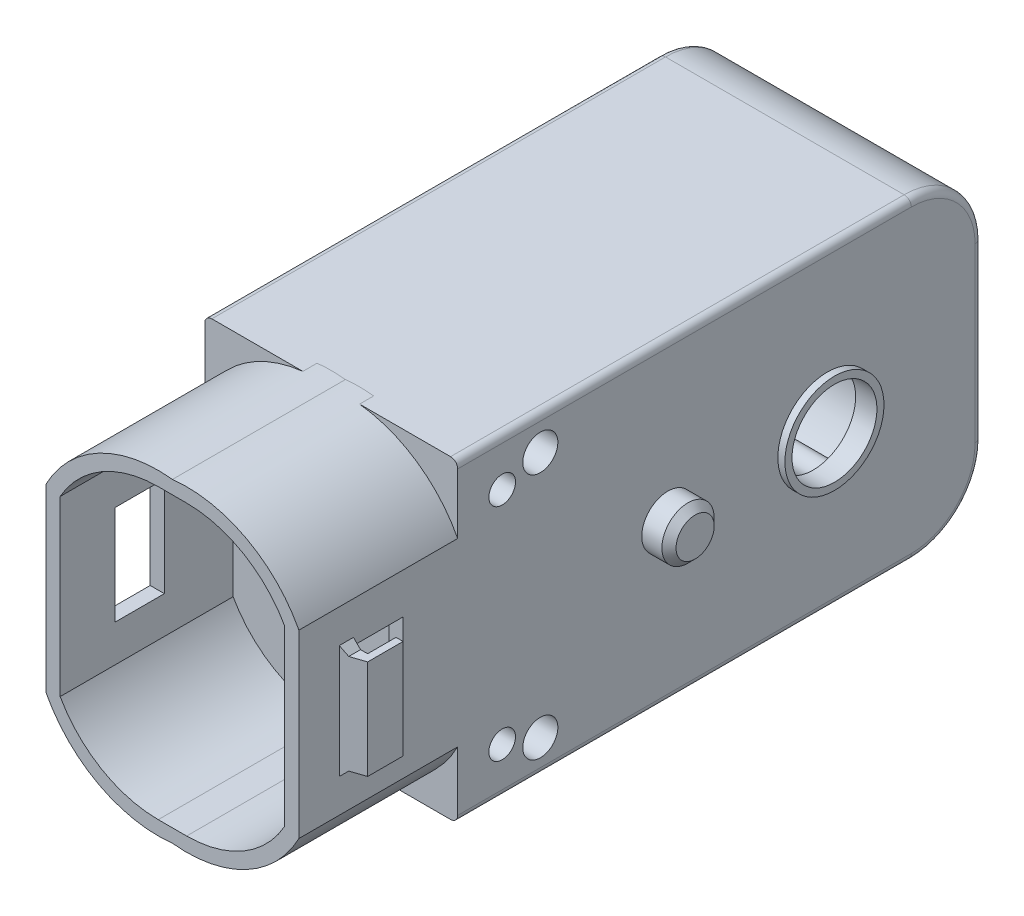
SolidWorks part; units mm, degrees
ref_plane "Front Plane" through (0, 0, 0) normal (0, 0, 1) x (1, 0, 0)
ref_plane "Top Plane" through (0, 0, 0) normal (0, 1, 0) x (1, 0, 0)
ref_plane "Right Plane" through (0, 0, 0) normal (1, 0, 0) x (0, 0, -1)
sketch "Sketch1" plane through (0, 0, 0) normal (0, 0, 1) x (1, 0, 0)
  line L0 (0, 11.115) -> (0, 10.1712)
  line L2 (-8.92, 6.365) -> (-8.92, -6.365)
  line L4 (-8.92, 6.365) -> (-8.92, -6.365) construction
  line L5 (55, 0) -> (-55, 0) construction
  line L7 (-7.92, 6.1126) -> (-7.92, -6.1126)
  line L8 (-1, 10.1712) -> (-1, -10.1712) construction
  line L9 (-1, 10.1712) -> (0, 10.1712)
  line L10 (-1, -10.1712) -> (0, -10.1712)
  line L11 (0, -10.1712) -> (0, -11.115)
  line L13 (0, 11.115) -> (0, -11.115) construction
  arc A0 (-8.92, 6.365) -> (0, 11.115) centre (-1, 2.2425) cw
  arc A1 (-8.92, -6.365) -> (0, -11.115) centre (-1, -2.2425) ccw
  arc A2 (-7.92, -6.1126) -> (-1, -10.1712) centre (-1, -2.2425) ccw
  arc A3 (-7.92, 6.1126) -> (-1, 10.1712) centre (-1, 2.2425) cw
  dimension "D1" = 22.23
  dimension "D2" = 12.73
  dimension "D3" = 1
extrude "Boss-Extrude1" add sketch "Sketch1" along normal blind 11.2
sketch "Sketch2" plane through (0, 0, 0) normal (0, 0, -1) x (-1, 0, 0)
  line L0 (0, -10.1712) -> (1, -10.1712) construction
  line L1 (2, 11.115) -> (8.92, 11.115)
  line L2 (0, 11.115) -> (0, 10.1712)
  line L3 (2.4484, -11.0529) -> (8.92, -11.0529)
  line L4 (8.92, 11.115) -> (8.92, -11.0529)
  line L5 (7.92, -6.1126) -> (7.92, 6.1126) construction
  line L6 (1, 10.1712) -> (0, 10.1712) construction
  line L7 (0, -10.1712) -> (1, -10.1712)
  line L8 (7.92, -6.1126) -> (7.92, 6.1126)
  line L9 (1, 10.1712) -> (0, 10.1712)
  line L10 (0, -10.1712) -> (0, -11.115)
  line L11 (8.92, 6.365) -> (8.92, -6.365) construction
  arc A0 (8.92, 6.365) -> (0, 11.115) centre (1, 2.2425) ccw construction
  arc A1 (2, 11.115) -> (0, 11.115) centre (1, 2.2425) ccw
  arc A2 (0, -11.115) -> (8.92, -6.365) centre (1, -2.2425) ccw construction
  arc A3 (0, -11.115) -> (2.4484, -11.0529) centre (1, -2.2425) ccw
  arc A4 (1, -10.1712) -> (7.92, -6.1126) centre (1, -2.2425) ccw construction
  arc A5 (7.92, 6.1126) -> (1, 10.1712) centre (1, 2.2425) ccw construction
  arc A6 (1, -10.1712) -> (7.92, -6.1126) centre (1, -2.2425) ccw
  arc A7 (7.92, 6.1126) -> (1, 10.1712) centre (1, 2.2425) ccw
extrude "Boss-Extrude2" add sketch "Sketch2" along normal blind 1
sketch "Sketch4" plane through (0, 0, -1) normal (0, 0, -1) x (-1, 0, 0)
  line L0 (0, -10.1712) -> (0, -11.115) construction
  line L1 (8.92, 11.115) -> (0, 11.115)
  line L2 (8.92, 11.115) -> (8.92, -11.0529)
  line L3 (8.92, -11.0529) -> (0, -11.0529)
  line L4 (0, 11.115) -> (0, 10.115)
  line L5 (2.4484, -11.0529) -> (8.92, -11.0529) construction
  line L6 (7.92, 10.115) -> (7.92, -10.0529)
  line L7 (7.92, -10.0529) -> (1, -10.0529)
  line L9 (7.92, 10.115) -> (1, 10.115)
  line L10 (1, 10.115) -> (0, 10.115)
  line L11 (1, -10.0529) -> (0, -10.0529)
  line L12 (0, -10.0529) -> (0, -11.0529)
  line L13 (1, 10.115) -> (1, -10.0529) construction
  line L15 (0, 11.115) -> (0, -11.0529) construction
  dimension "D1" = 1
extrude "Boss-Extrude4" add sketch "Sketch4" along normal blind 36
sketch "Sketch5" plane through (0, 0, -37) normal (0, 0, -1) x (-1, 0, 0)
  line L1 (0, 11.115) -> (8.92, 11.115)
  line L2 (0, 11.115) -> (0, -11.0529)
  line L3 (0, -11.0529) -> (8.92, -11.0529)
  line L4 (8.92, 11.115) -> (8.92, -11.0529)
extrude "Boss-Extrude6" add sketch "Sketch5" against normal blind 2
fillet "Fillet2" radius 5 4 edges at (-3.96, -10.0529, -35) (-3.96, 10.115, -35) (-4.46, -11.0529, -37) (-4.46, 11.115, -37)
sketch "Sketch6" plane through (0, 0, -37) normal (0, 0, -1) x (-1, 0, 0)
  line L0 (0, 0) -> (1.4, 0) construction
  line L1 (0, 6.115) -> (0, -6.0529) construction
  line L2 (1.4, -2.5) -> (0, -2.5)
  line L3 (1.4, -2.5) -> (1.4, 2.5)
  line L4 (1.4, 2.5) -> (0, 2.5)
  line L5 (0, -2.5) -> (0, 2.5)
  line L6 (1.4, -2.5) -> (0, 2.5) construction
  line L7 (1.4, 2.5) -> (0, -2.5) construction
  point P3 (0.7, 0)
  dimension "D1" = 1.4
  dimension "D2" = 5
extrude "Boss-Extrude7" add sketch "Sketch6" along normal blind 4.8
sketch "Sketch7" plane through (-1.4, 0, 0) normal (-1, 0, 0) x (0, 0, 1)
  line L0 (-39.4, 2.5) -> (-39.4, -2.5) construction
  line L1 (-41.8, 2.5) -> (-37, 2.5) construction
  line L2 (-41.8, -2.5) -> (-37, -2.5) construction
  line L3 (-37, -2.5) -> (-37, 2.5) construction
  circle A0 centre (-39.4, 0) radius 1.38
  dimension "D1" = 2.76
extrude "Cut-Extrude1" cut sketch "Sketch7" against normal blind 4.8
sketch "Sketch8" plane through (-8.92, 0, 0) normal (-1, 0, 0) x (0, 0, 1)
  line L0 (-37, 0) -> (-26.08, 0) construction
  line L1 (-37, -2.5) -> (-37, 2.5) construction
  circle A0 centre (-26.08, 0) radius 3.495
  circle A2 centre (-26.08, 0) radius 2.995
  dimension "D2" = 6.99
  dimension "D3" = 0.5
  dimension "D1" = 10.92
extrude "Boss-Extrude8" add sketch "Sketch8" along normal blind 0.5
sketch "Sketch9" plane through (-8.92, 0, 0) normal (-1, 0, 0) x (0, 0, 1)
  circle A1 centre (-26.08, 0) radius 2.995
  circle A2 centre (-26.08, 0) radius 2.995
  dimension "D1" = 0
extrude "Cut-Extrude2" cut sketch "Sketch9" against normal blind 7.5
chamfer "Chamfer1" distance 1 angle 45 2 edges at (-0.7, -2.5, -37) (-0.7, 2.5, -37)
sketch "Sketch10" plane through (-8.92, 0, 0) normal (-1, 0, 0) x (0, 0, 1)
  line L0 (-26.08, 0) -> (-14.83, 0) construction
  circle A0 centre (-14.83, 0) radius 1.845
  dimension "D2" = 3.69
  dimension "D1" = 11.25
extrude "Boss-Extrude9" add sketch "Sketch10" along normal blind 1.92
chamfer "Chamfer2" distance 0.5 angle 45 1 edges at (-10.84, 0, -12.985)
sketch "Sketch11" plane through (-8.92, 0, 0) normal (-1, 0, 0) x (0, 0, 1)
  line L0 (-14.83, 0) -> (-5.83, 0) construction
  line L1 (-5.83, 8.71) -> (-5.83, -8.71) construction
  line L2 (-37, -6.0529) -> (-37, 6.115) construction
  circle A0 centre (-5.83, 8.71) radius 1.5
  circle A1 centre (-5.83, -8.71) radius 1.5
  dimension "D4" = 3
  dimension "D1" = 31.17
  dimension "D2" = 17.42
extrude "Cut-Extrude3" cut sketch "Sketch11" against normal blind 1.92
sketch "Sketch12" plane through (-8.92, 0, 0) normal (-1, 0, 0) x (0, 0, 1)
  line L0 (5.962, 0) -> (-5.962, 0) construction
  circle A0 centre (-3.14, 7.7815) radius 1.15
  circle A1 centre (-3.14, -7.7815) radius 1.15
  dimension "D1" = 2.3
extrude "Cut-Extrude4" cut sketch "Sketch12" against normal blind 1.92
ref_plane "Plane1" through (0, 0, -1) normal (0, 0, -1) x (-1, 0, 0)
sketch "Sketch13" plane through (0, 0, -1) normal (0, 0, -1) x (-1, 0, 0)
  line L0 (0, -10.1712) -> (1, -10.1712) construction
  line L1 (7.92, 10.115) -> (0, 10.115)
  line L2 (7.92, 10.115) -> (7.92, -10.1712)
  line L3 (7.92, -10.1712) -> (0.5, -10.1712)
  line L4 (0, 10.115) -> (0, 2.5)
  line L6 (0, 10.115) -> (0, 5.115) construction
  line L7 (5.962, 0) -> (-5.962, 0) construction
  line L8 (0, -10.115) -> (0, -2.5)
  line L9 (0.5, -10.1712) -> (0, -10.1712)
  line L10 (0, -10.1712) -> (0, -10.115)
  arc A0 (0, -2.5) -> (0, 2.5) centre (0, 0) ccw
  dimension "D1" = 5
extrude "Boss-Extrude13" add sketch "Sketch13" along normal blind 0.5
sketch "Sketch14" plane through (-8.92, 0, 0) normal (-1, 0, 0) x (0, 0, 1)
  line L0 (5.6, 6.365) -> (5.6, -6.365) construction
  line L1 (11.2, 6.365) -> (0, 6.365) construction
  line L2 (11.2, -6.365) -> (0, -6.365) construction
  line L4 (7.35, -3.5) -> (3.85, -3.5)
  line L5 (7.35, -3.5) -> (7.35, 3.5)
  line L6 (7.35, 3.5) -> (3.85, 3.5)
  line L7 (3.85, -3.5) -> (3.85, 3.5)
  line L8 (7.35, -3.5) -> (3.85, 3.5) construction
  line L9 (7.35, 3.5) -> (3.85, -3.5) construction
  point P6 (5.6, 0)
  dimension "D1" = 7
  dimension "D2" = 3.5
extrude "Cut-Extrude6" cut sketch "Sketch14" against normal blind 5.5
sketch "Sketch15" plane through (0, 3.5, 0) normal (0, -1, 0) x (1, 0, 0)
  line L0 (-8.92, 7.35) -> (-10.42, 7.35)
  line L1 (-10.42, 7.85) -> (-8.92, 8.35)
  line L2 (-8.92, 11.2) -> (-8.92, 0) construction
  line L3 (-8.92, 8.35) -> (-8.92, 7.35)
  line L4 (-10.42, 7.85) -> (-10.42, 7.35)
  dimension "D1" = 1.5
  dimension "D2" = 0.5
  dimension "D3" = 1
extrude "Boss-Extrude14" add sketch "Sketch15" along normal blind 7
sketch "Sketch16" plane through (0, 0, 7.35) normal (0, 0, -1) x (-1, 0, 0)
  line L0 (10.42, -3.5) -> (8.92, -3.5) construction
  line L1 (10.42, 3.5) -> (9.92, 3.5)
  line L2 (10.42, 3.5) -> (10.42, -3.5)
  line L3 (10.42, -3.5) -> (9.92, -3.5)
  line L4 (9.92, 3.5) -> (9.92, -3.5)
extrude "Boss-Extrude16" add sketch "Sketch16" along normal blind 2
chamfer "Chamfer3" distance 0.5 angle 45 2 edges at (-8.92, -3.5, 7.85) (-8.92, 3.5, 7.85)
sketch "Sketch20" plane through (-7.92, 0, 0) normal (1, 0, 0) x (0, 0, -1)
  line L0 (16.175, 0) -> (16.675, 0) construction
  circle A3 centre (14.83, 0) radius 1.345 construction
  circle A4 centre (14.83, 0) radius 1.845 construction
  circle A5 centre (16.425, 0) radius 0.5
extrude "Boss-Extrude19" add sketch "Sketch20" along normal blind 15
sketch "Sketch21" plane through (-7.92, 0, 0) normal (1, 0, 0) x (0, 0, -1)
  line L0 (9.856, 0) -> (-9.856, 0) construction
  circle A0 centre (5.83, 8.71) radius 1.5
  circle A1 centre (3.14, 7.7815) radius 1.15
  circle A2 centre (5.83, 8.71) radius 1.238
  circle A3 centre (3.14, 7.7815) radius 0.9401
  circle A4 centre (3.14, -7.7815) radius 0.9401
  circle A5 centre (5.83, -8.71) radius 1.238
  circle A6 centre (3.14, -7.7815) radius 1.15
  circle A7 centre (5.83, -8.71) radius 1.5
extrude "Boss-Extrude23" add sketch "Sketch21" against normal blind 1
extrude "Boss-Extrude24" add sketch "Sketch21<2>" along normal blind 8
sketch "Sketch21<2>" plane through (-7.92, 0, 0) normal (1, 0, 0) x (0, 0, -1) same geometry as "Sketch21"
sketch "Sketch22" plane through (-7.92, 0, 0) normal (1, 0, 0) x (0, 0, -1)
  line L0 (9.856, 0) -> (-9.856, 0) construction
  circle A0 centre (17.5264, 9.0814) radius 0.5
  circle A1 centre (17.5264, 9.0814) radius 0.8
  circle A2 centre (31.7978, 8.5923) radius 0.5
  circle A3 centre (31.7978, 8.5923) radius 0.8
  circle A4 centre (31.7978, -8.5923) radius 0.8
  circle A5 centre (31.7978, -8.5923) radius 0.5
  circle A6 centre (17.5264, -9.0814) radius 0.8
  circle A7 centre (17.5264, -9.0814) radius 0.5
extrude "Boss-Extrude25" add sketch "Sketch22" along normal blind 8
mirror "Mirror7" about plane through (0, 0, 0) normal (1, 0, 0) of bodies 131
fillet "Fillet4" radius 0.5 10 edges at (-8.92, -11.0529, -16) (-8.92, -9.5885, -35.5355) (-8.92, 0.031, -37) (-8.92, 9.6505, -35.5355) (8.92, -11.0529, -16) (8.92, -9.5885, -35.5355) (8.92, 0.031, -37) (8.92, 9.6505, -35.5355) (-8.92, 11.115, -16) (8.92, 11.115, -16)
